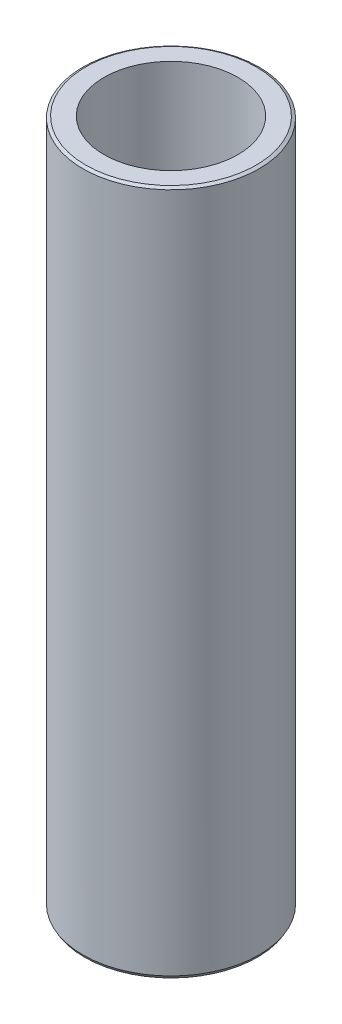
SolidWorks part; units mm, degrees
ref_plane "Front Plane" through (0, 0, 0) normal (0, 0, 1) x (1, 0, 0)
ref_plane "Top Plane" through (0, 0, 0) normal (0, 1, 0) x (1, 0, 0)
ref_plane "Right Plane" through (0, 0, 0) normal (1, 0, 0) x (0, 0, -1)
sketch "Sketch1" plane through (0, 0, 0) normal (0, 1, 0) x (1, 0, 0)
  circle A0 centre (0, 0) radius 55
  dimension "SHAFT_OD" = 110
extrude "Boss-Extrude1" add sketch "Sketch1" along normal blind 427.9166
sketch "Sketch2" plane through (0, 0, 0) normal (0, 1, 0) x (1, 0, 0)
  circle A0 centre (0, 0) radius 41.8182
  dimension "BORE_D" = 83.6364
extrude "Cut-Extrude1" cut sketch "Sketch2" along normal through all
chamfer "Chamfer1" distance 1.0494 angle 60 2 edges at (0, 427.9166, 55) (0, 0, 55) first distance on face at (0, 427.9166, 55) first distance on face at (0, 0, 41.8182)
